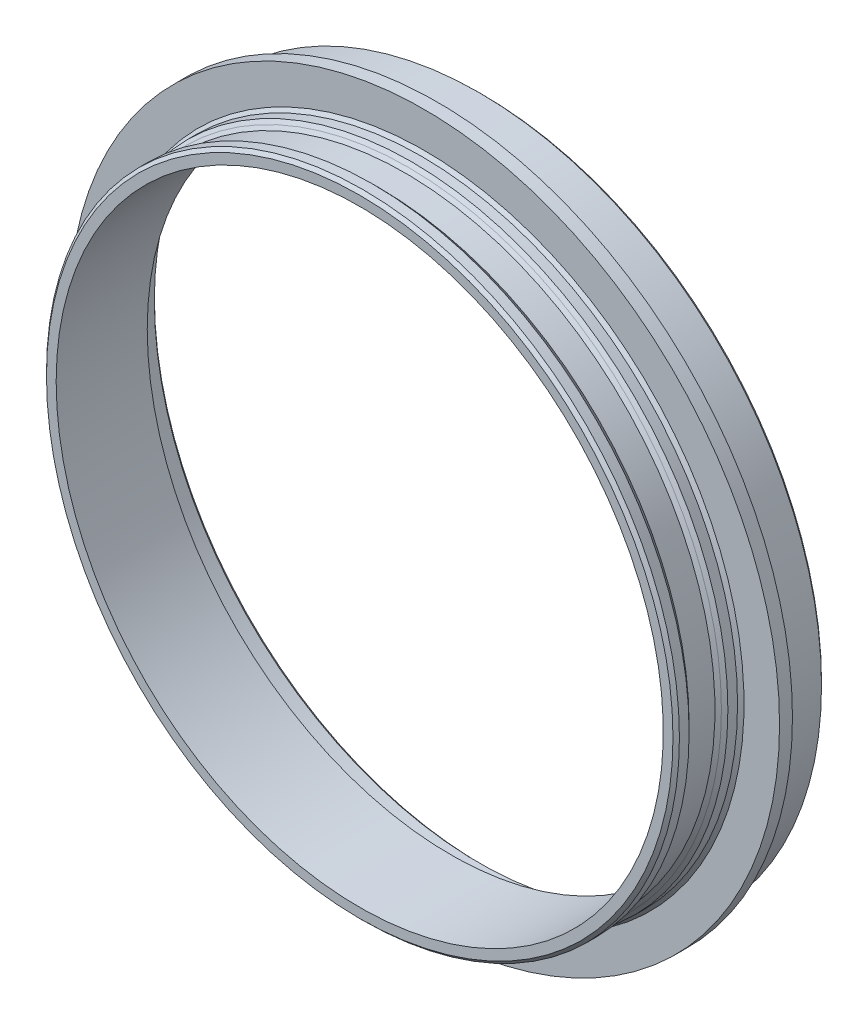
SolidWorks part; units mm, degrees
ref_plane "Front Plane" through (0, 0, 0) normal (0, 0, 1) x (1, 0, 0)
ref_plane "Top Plane" through (0, 0, 0) normal (0, 1, 0) x (1, 0, 0)
ref_plane "Right Plane" through (0, 0, 0) normal (1, 0, 0) x (0, 0, -1)
sketch "Sketch1" plane through (0, 0, 0) normal (0, 1, 0) x (1, 0, 0)
  line L0 (0, 69.1698) -> (0, -39.1508) construction
  line L1 (-62.5573, 0) -> (61.2977, 0) construction
  line L2 (50.3, 19) -> (50.3, 14.1)
  line L3 (50.3, 14.1) -> (47, 14.1)
  line L8 (49, 0) -> (49, 2.5)
  line L9 (49, 10) -> (55, 10)
  line L10 (55, 10) -> (55, 12)
  line L11 (55, 12) -> (53, 12)
  line L12 (53, 12) -> (53, 19)
  line L13 (53, 19) -> (50.3, 19)
  line L14 (49, 7.5) -> (48, 7.5)
  line L15 (48, 7.5) -> (48, 2.5)
  line L16 (48, 2.5) -> (49, 2.5)
  line L17 (49, 7.5) -> (49, 10)
  line L21 (47, 14.1) -> (47, 0)
  line L22 (47, 0) -> (49, 0)
  dimension "D1" = 55
  dimension "D3" = 53
  dimension "D4" = 2.7
  dimension "D5" = 4.9
  dimension "D6" = 7
  dimension "D7" = 2
  dimension "D8" = 49
  dimension "D9" = 2
  dimension "D10" = 10
  dimension "D12" = 1
  dimension "D13" = 5
  dimension "D14" = 2.5
revolve "Revolve1" add sketch "Sketch1" angle 360 about L0
chamfer "Chamfer1" distance 0.5 angle 45 8 edges at (-48, 0, -2.5) (-49, 0, -2.5) (-48, 0, -7.5) (-49, 0, -7.5) (-53, 0, -19) (-50.3, 0, -19) (-49, 0, -10) (-49, 0, 0)
